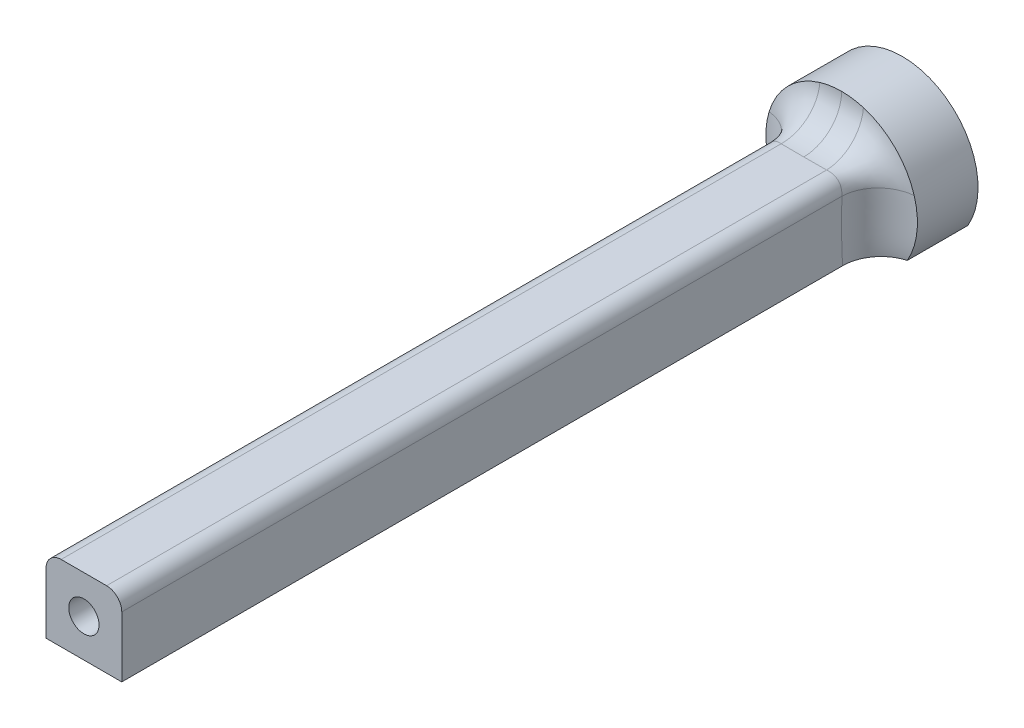
SolidWorks part; units mm, degrees
ref_plane "Front Plane" through (0, 0, 0) normal (0, 0, 1) x (1, 0, 0)
ref_plane "Top Plane" through (0, 0, 0) normal (0, 1, 0) x (1, 0, 0)
ref_plane "Right Plane" through (0, 0, 0) normal (1, 0, 0) x (0, 0, -1)
sketch "Sketch1" plane through (0, 0, 0) normal (0, 0, 1) x (1, 0, 0)
  line L1 (5, -5) -> (-5, -5)
  line L2 (5, -5) -> (5, 5)
  line L3 (5, 5) -> (-5, 5)
  line L4 (-5, -5) -> (-5, 5)
  line L5 (5, -5) -> (-5, 5) construction
  line L6 (5, 5) -> (-5, -5) construction
  point P0 (-4.9955, 7.6879)
  dimension "D2" = 10
extrude "Boss-Extrude1" add sketch "Sketch1" along normal blind 108
fillet "Fillet1" radius 2 2 edges at (-5, 5, 54) (5, 5, 54)
sketch "Sketch3" plane through (0, 0, 108) normal (0, 0, 1) x (1, 0, 0)
  circle A0 centre (0, 0) radius 2
  dimension "D1" = 4
extrude "Cut-Extrude1" cut sketch "Sketch3" against normal blind 20 draft 2
sketch "Sketch4" plane through (0, 0, 0) normal (0, 0, -1) x (-1, 0, 0)
  line L0 (-8.6603, -5) -> (8.6603, -5)
  line L1 (5, -5) -> (-5, -5) construction
  circle A0 centre (0, 0) radius 10
  line M3 (5, -5) -> (5, 3)
  arc M4 (5, 3) -> (3, 5) centre (3, 3) ccw
  line M5 (3, 5) -> (-3, 5)
  arc M6 (-3, 5) -> (-5, 3) centre (-3, 3) ccw
  line M7 (-5, 3) -> (-5, -5)
  line M8 (-5, -5) -> (5, -5)
  dimension "D1" = 20
extrude "Boss-Extrude3" add sketch "Sketch4" against normal blind 8 contours L0 A0 M7 M6 M5 M4 M3 | M8 M3 M4 M5 M6 M7 region at (2.5235, 9.4178, 0) region at (0, -0.0795, 0)
fillet "Fillet2" radius 5 3 edges at (-5, -1, 8) (0, 5, 8) (5, -1, 8)
